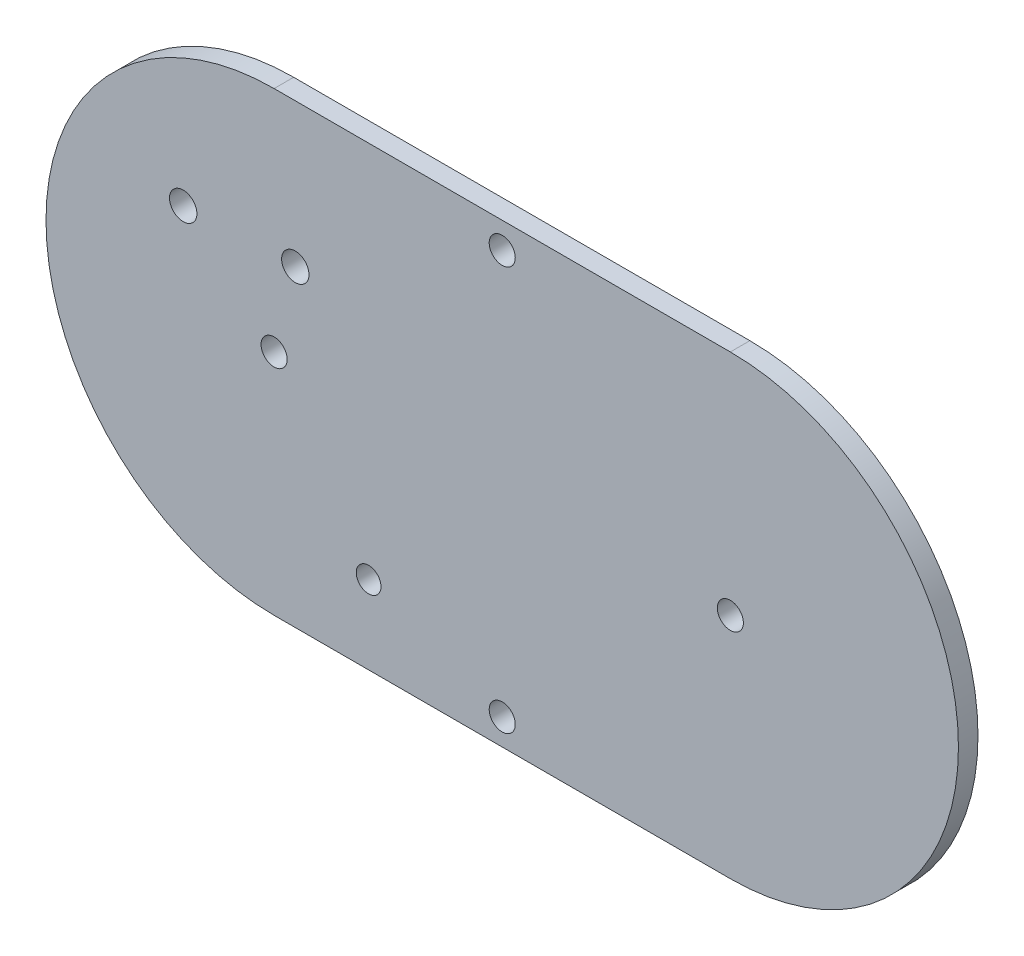
SolidWorks part; units mm, degrees
ref_plane "Front Plane" through (0, 0, 0) normal (0, 0, 1) x (1, 0, 0)
ref_plane "Top Plane" through (0, 0, 0) normal (0, 1, 0) x (1, 0, 0)
ref_plane "Right Plane" through (0, 0, 0) normal (1, 0, 0) x (0, 0, -1)
sketch "Sketch1" plane through (0, 0, 0) normal (0, 0, 1) x (1, 0, 0)
  line L0 (278.5146, 346.2873) -> (278.5146, 276.2873) construction
  line L1 (243.5146, 346.2873) -> (313.5146, 346.2873)
  line L3 (243.5146, 276.2873) -> (313.5146, 276.2873)
  line L12 (208.5146, 311.2873) -> (348.5146, 311.2873) construction
  arc A0 (243.5146, 346.2873) -> (243.5146, 276.2873) centre (243.5146, 311.2873) ccw
  arc A1 (313.5146, 346.2873) -> (313.5146, 276.2873) centre (313.5146, 311.2873) cw
  circle A2 centre (243.5146, 311.2873) radius 2
  circle A3 centre (313.5146, 311.2873) radius 2
  circle A4 centre (246.7646, 324.2256) radius 2.1
  circle A5 centre (229.5646, 323.7256) radius 2.1
  circle A6 centre (278.5146, 342.2873) radius 2
  circle A7 centre (278.5146, 280.2873) radius 2
  circle A8 centre (258.0146, 288.2873) radius 1.9
  point P45 (278.5146, 342.2873)
  dimension "D3" = 4
  dimension "D4" = 4
  dimension "D7" = 4
  dimension "D8" = 3.8
  dimension "D1" = 70
  dimension "D2" = 70
  dimension "D5" = 12.9383
  dimension "D6" = 4
  dimension "D9" = 12.4383
  dimension "D10" = 17.2
  dimension "D11" = 12
  dimension "D12" = 20.5
extrude "Boss-Extrude1" add sketch "Sketch1" along normal blind 3
